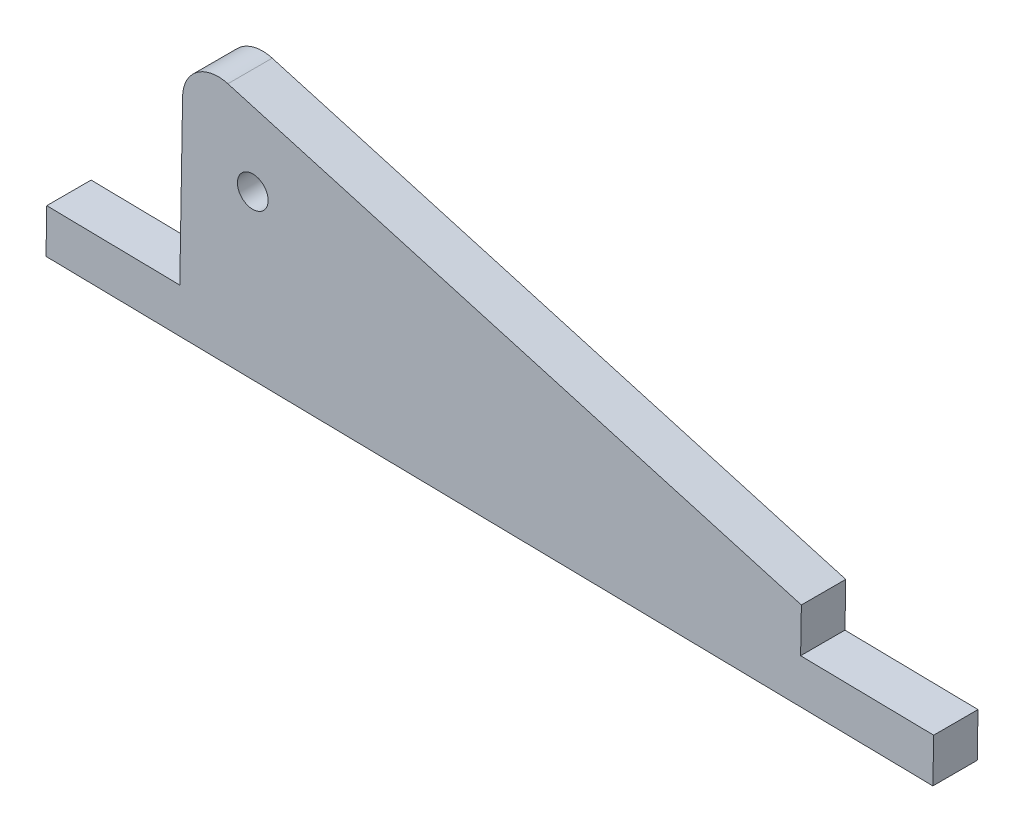
SolidWorks part; units mm, degrees
material "Balsa"
ref_plane "Front Plane" through (0, 0, 0) normal (0, 0, 1) x (1, 0, 0)
ref_plane "Top Plane" through (0, 0, 0) normal (0, 1, 0) x (1, 0, 0)
ref_plane "Right Plane" through (0, 0, 0) normal (1, 0, 0) x (0, 0, -1)
ref_plane "Plane1" through (0, 0, 41.275) normal (0, 0, -1) x (-1, 0, 0)
sketch "Sketch4" plane through (0, 0, 41.275) normal (0, 0, -1) x (-1, 0, 0)
  line L1 (205.9734, 28.3169) -> (215.497, 28.4793)
  line L2 (205.9734, 28.3169) -> (206.0275, 25.1424)
  line L3 (206.0275, 25.1424) -> (269.5183, 26.2253)
  line L4 (269.4641, 29.3998) -> (269.5183, 26.2253)
  line L5 (215.497, 28.4793) -> (215.4428, 31.6543)
  line L6 (259.9405, 29.2374) -> (259.8864, 32.4124)
  line L8 (259.9405, 29.2374) -> (269.4641, 29.3998)
  line L9 (259.8864, 32.4124) -> (259.6827, 44.3543)
  line L10 (259.6827, 44.3543) -> (215.4428, 31.6543)
  circle A0 centre (254.7164, 37.6435) radius 1.1
  circle A1 centre (92.5502, 37.0791) radius 1.1 construction
  dimension "D1" = 3.175
  dimension "0.125" = 3.175
  dimension "1.75" = 44.45
  dimension "D2" = 12.7
  dimension "D3" = 5.08
  dimension "0.20" = 5.08
extrude "Boss-Extrude2" add sketch "Sketch4" along normal blind 1.5875 and the other way blind 1.5875
fillet "Fillet2" radius 2.54 1 edges at (-259.6827, 44.3543, 41.275)
